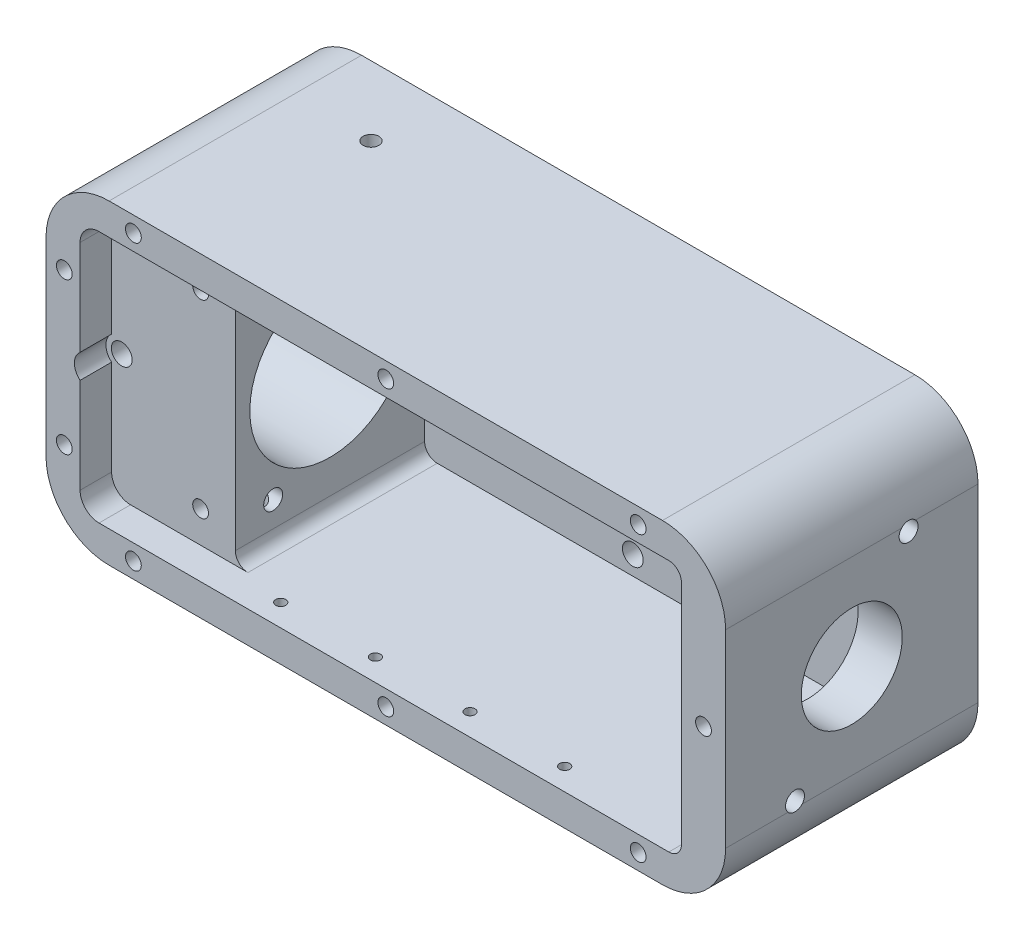
SolidWorks part; units mm, degrees
material "6061 Alloy"
ref_plane "Front" through (0, 0, 0) normal (0, 0, 1) x (1, 0, 0)
ref_plane "Top" through (0, 0, 0) normal (0, 1, 0) x (1, 0, 0)
ref_plane "Right" through (0, 0, 0) normal (1, 0, 0) x (0, 0, -1)
ref_plane "Plane1" through (0, 0, 40) normal (0, 0, 1) x (1, 0, 0)
sketch "Sketch1" plane through (0, 0, 40) normal (0, 0, 1) x (1, 0, 0)
  line L0 (0, -50) -> (107.7, -50)
  line L1 (107.7, -50) -> (107.7, 0)
  line L2 (107.7, 0) -> (0, 0)
  line L3 (0, 0) -> (0, -50)
extrude "Boss-Extrude1" add sketch "Sketch1" against normal blind 40
sketch "Sketch2" plane through (0, 0, 40) normal (0, 0, 1) x (1, 0, 0)
  line L0 (100.7, -45) -> (100.7, -5)
  line L1 (100.7, -5) -> (25, -5)
  line L2 (25, -5) -> (25, -45)
  line L3 (25, -45) -> (100.7, -45)
extrude "Cut-Extrude1" cut sketch "Sketch2" against normal blind 35
ref_plane "Plane2" through (0, 0, 35) normal (0, 0, -1) x (-1, 0, 0)
sketch "Sketch4" plane through (0, 0, 35) normal (0, 0, -1) x (-1, 0, 0)
  line L0 (-5.4, -5) -> (-25, -5)
  line L1 (-25, -5) -> (-25, -45)
  line L2 (-25, -45) -> (-5.4, -45)
  line L3 (-5.4, -45) -> (-5.4, -5)
extrude "Cut-Extrude2" cut sketch "Sketch4" against normal up to surface up to plane "Plane1"
sketch "Sketch5" plane through (0, 0, 0) normal (0, 0, -1) x (-1, 0, 0)
  line L0 (-99.7, -30.15) -> (-54.7, -30.15)
  line L1 (-54.7, -30.15) -> (-54.7, -19.85)
  line L2 (-54.7, -19.85) -> (-99.7, -19.85)
  line L3 (-99.7, -19.85) -> (-99.7, -30.15)
extrude "Cut-Extrude3" cut sketch "Sketch5" against normal through all
hole_wizard "M4x0.7 Tapped Hole1" positions "Sketch7" profile "Sketch6" tap size "M4x0.7" standard "ANSI Metric" end condition through all
sketch "Sketch7" plane through (0, 0, 0) normal (0, 0, -1) x (-1, 0, 0)
  point P0 (-58, -42)
  point P1 (-78, -42)
  point P2 (-98, -42)
  point P3 (-98, -8)
  point P4 (-58, -8)
  point P5 (-78, -8)
sketch "Sketch6" plane through (58, -42, 0) normal (1, 0, 0) x (0, 1, 0)
  line L0 (0, 0) -> (0, 40)
  line L1 (0, 40) -> (1.65, 40)
  line L2 (1.65, 40) -> (1.65, 0)
  line L5 (1.65, 0) -> (0, 0)
  line L11 (0, -6.35) -> (0, 107.95) construction
  dimension "Thru Tap Drill Dia." = 3.3
  dimension "Thru Tap Drill Depth" = 40
hole_wizard "Ø3.0mm Dowel Hole1" positions "Sketch9" profile "Sketch8" hole size "Ø3.0" standard "ANSI Metric" end condition through all
sketch "Sketch9" plane through (100.7, 0, 0) normal (-1, 0, 0) x (0, 0, 1)
  point P0 (11, -11)
sketch "Sketch8" plane through (100.7, -11, 11) normal (0, 1, 0) x (0, 0, 1)
  line L0 (0, 0) -> (0, 7)
  line L1 (0, 7) -> (1.5, 7)
  line L2 (1.5, 7) -> (1.5, 0)
  line L5 (1.5, 0) -> (0, 0)
  line L11 (0, -6.35) -> (0, 107.95) construction
  dimension "Thru Hole Dia." = 3
  dimension "Thru Hole Depth" = 7
hole_wizard "Ø3.0mm Dowel Hole2" positions "Sketch11" profile "Sketch10" hole size "Ø3.0" standard "ANSI Metric" end condition up to next
sketch "Sketch11" plane through (107.7, 0, 0) normal (1, 0, 0) x (0, 0, -1)
  point P0 (-29, -39)
sketch "Sketch10" plane through (107.7, -39, 29) normal (0, 1, 0) x (0, 0, -1)
  line L0 (0, 0) -> (0, 7)
  line L1 (0, 7) -> (1.5, 7)
  line L2 (1.5, 7) -> (1.5, 0)
  line L5 (1.5, 0) -> (0, 0)
  line L11 (0, -6.35) -> (0, 107.95) construction
  dimension "Thru Hole Dia." = 3
  dimension "Thru Hole Depth" = 7
hole_wizard "M3x0.5 Tapped Hole1" positions "Sketch13" profile "Sketch12" tap size "M3x0.5" standard "ANSI Metric"
sketch "Sketch13" plane through (0, 0, 0) normal (0, 1, 0) x (1, 0, 0)
  point P0 (22.5, -11)
sketch "Sketch12" plane through (22.5, 0, 11) normal (1, 0, 0) x (0, 0, 1)
  line L0 (0, 0) -> (0, 8.2511)
  line L1 (0, 8.2511) -> (1.25, 7.5)
  line L2 (1.25, 7.5) -> (1.25, 0)
  line L5 (1.25, 0) -> (0, 0)
  line L10 (0, 8.2511) -> (-1.25, 7.5) construction
  line L11 (0, -6.35) -> (0, 107.95) construction
  dimension "Tap Drill Dia." = 2.5
  dimension "Tap Drill Depth" = 7.5
  dimension "Drill Angle" = 118
hole_wizard "Ø3.0mm Dowel Hole3" positions "Sketch15" profile "Sketch14" hole size "Ø3.0" standard "ANSI Metric" end condition through all
sketch "Sketch15" plane through (25, 0, 0) normal (1, 0, 0) x (0, 0, -1)
  point P0 (-11, -11)
sketch "Sketch14" plane through (25, -11, 11) normal (0, 1, 0) x (0, 0, -1)
  line L0 (0, 0) -> (0, 25)
  line L1 (0, 25) -> (1.5, 25)
  line L2 (1.5, 25) -> (1.5, 0)
  line L5 (1.5, 0) -> (0, 0)
  line L11 (0, -6.35) -> (0, 107.95) construction
  dimension "Thru Hole Dia." = 3
  dimension "Thru Hole Depth" = 25
hole_wizard "Hole1" positions "Sketch17" profile "Sketch16" legacy
sketch "Sketch17" plane through (100.7, 0, 0) normal (-1, 0, 0) x (0, 0, 1)
  point P0 (20, -25)
sketch "Sketch16" plane through (100.7, -25, 20) normal (0, 1, 0) x (0, 0, 1)
  line L0 (0, 0) -> (0, 7)
  line L1 (0, 7) -> (8, 7)
  line L2 (8, 7) -> (8, 0)
  line L3 (8, 0) -> (0, 0)
  line L4 (0, 110) -> (0, -10) construction
  dimension "Diameter" = 16
  dimension "Depth" = 7
hole_wizard "M3x0.5 Tapped Hole2" positions "Sketch19" profile "Sketch18" tap size "M3x0.5" standard "ANSI Metric"
sketch "Sketch19" plane through (0, 0, 40) normal (0, 0, 1) x (1, 0, 0)
  point P0 (104.2, -25)
sketch "Sketch18" plane through (104.2, -25, 40) normal (1, 0, 0) x (0, -1, 0)
  line L0 (0, 0) -> (0, 8.2511)
  line L1 (0, 8.2511) -> (1.25, 7.5)
  line L2 (1.25, 7.5) -> (1.25, 0)
  line L5 (1.25, 0) -> (0, 0)
  line L10 (0, 8.2511) -> (-1.25, 7.5) construction
  line L11 (0, -6.35) -> (0, 107.95) construction
  dimension "Tap Drill Dia." = 2.5
  dimension "Tap Drill Depth" = 7.5
  dimension "Drill Angle" = 118
hole_wizard "Ø3.0mm Dowel Hole4" positions "Sketch21" profile "Sketch20" hole size "Ø3.0" standard "ANSI Metric" end condition through all
sketch "Sketch21" plane through (0, 0, 0) normal (-1, 0, 0) x (0, 0, 1)
  point P0 (29, -39)
sketch "Sketch20" plane through (0, -39, 29) normal (0, 1, 0) x (0, 0, 1)
  line L0 (0, 0) -> (0, 107.7)
  line L1 (0, 107.7) -> (1.5, 107.7)
  line L2 (1.5, 107.7) -> (1.5, 0)
  line L5 (1.5, 0) -> (0, 0)
  line L11 (0, -6.35) -> (0, 107.95) construction
  dimension "Thru Hole Dia." = 3
  dimension "Thru Hole Depth" = 107.7
hole_wizard "M3x0.5 Tapped Hole3" positions "Sketch23" profile "Sketch22" tap size "M3x0.5" standard "ANSI Metric"
sketch "Sketch23" plane through (0, 0, 40) normal (0, 0, 1) x (1, 0, 0)
  point P0 (2.9, -37)
  point P1 (93.85, -2.5)
  point P2 (53.85, -2.5)
  point P3 (13.85, -2.5)
  point P4 (2.9, -13)
  point P5 (13.85, -47.5)
  point P6 (53.85, -47.5)
  point P7 (93.85, -47.5)
sketch "Sketch22" plane through (2.9, -37, 40) normal (1, 0, 0) x (0, -1, 0)
  line L0 (0, 0) -> (0, 8.2511)
  line L1 (0, 8.2511) -> (1.25, 7.5)
  line L2 (1.25, 7.5) -> (1.25, 0)
  line L5 (1.25, 0) -> (0, 0)
  line L10 (0, 8.2511) -> (-1.25, 7.5) construction
  line L11 (0, -6.35) -> (0, 107.95) construction
  dimension "Tap Drill Dia." = 2.5
  dimension "Tap Drill Depth" = 7.5
  dimension "Drill Angle" = 118
hole_wizard "M3x0.5 Tapped Hole4" positions "Sketch25" profile "Sketch24" tap size "M3x0.5" standard "ANSI Metric" end condition up to next
sketch "Sketch25" plane through (0, -50, 0) normal (0, -1, 0) x (-1, 0, 0)
  point P0 (-22.5, -29)
sketch "Sketch24" plane through (22.5, -50, 29) normal (1, 0, 0) x (0, 0, -1)
  line L0 (0, 0) -> (0, 9.5)
  line L1 (0, 9.5) -> (1.25, 9.5)
  line L2 (1.25, 9.5) -> (1.25, 0)
  line L5 (1.25, 0) -> (0, 0)
  line L11 (0, -6.35) -> (0, 107.95) construction
  dimension "Thru Tap Drill Dia." = 2.5
  dimension "Thru Tap Drill Depth" = 9.5
hole_wizard "1 (1) Diameter Hole1" positions "Sketch27" profile "Sketch26" hole size "1" standard "ANSI Inch"
sketch "Sketch27" plane through (0, 0, 0) normal (-1, 0, 0) x (0, 0, 1)
  point P0 (20, -25)
sketch "Sketch26" plane through (0, -25, 20) normal (0, 1, 0) x (0, 0, 1)
  line L0 (0, 0) -> (0, 25)
  line L1 (0, 25) -> (12.7, 25)
  line L2 (12.7, 25) -> (12.7, 0)
  line L5 (12.7, 0) -> (0, 0)
  line L11 (0, -6.35) -> (0, 107.95) construction
  dimension "Thru Hole Dia." = 25.4
  dimension "Thru Hole Depth" = 25
ref_plane "Plane3" through (0, 0, 32.5924) normal (0, 0, -1) x (-1, 0, 0)
hole_wizard "M4x0.7 Tapped Hole2" positions "Sketch29" profile "Sketch28" tap size "M4x0.7" standard "ANSI Metric" end condition through all
sketch "Sketch29" plane through (0, 0, 32.5924) normal (0, 0, -1) x (-1, 0, 0)
  point P0 (-7, -25)
sketch "Sketch28" plane through (7, -25, 32.5924) normal (1, 0, 0) x (0, 1, 0)
  line L0 (0, 0) -> (0, 7.4076)
  line L1 (0, 7.4076) -> (1.65, 7.4076)
  line L2 (1.65, 7.4076) -> (1.65, 0)
  line L5 (1.65, 0) -> (0, 0)
  line L11 (0, -6.35) -> (0, 107.95) construction
  dimension "Thru Tap Drill Dia." = 3.3
  dimension "Thru Tap Drill Depth" = 7.4076
hole_wizard "M3x0.5 Tapped Hole5" positions "Sketch31" profile "Sketch30" tap size "M3x0.5" standard "ANSI Metric"
sketch "Sketch31" plane through (0, 0, 35) normal (0, 0, 1) x (1, 0, 0)
  point P0 (19.5, -10)
  point P1 (19.5, -40)
sketch "Sketch30" plane through (19.5, -10, 35) normal (1, 0, 0) x (0, -1, 0)
  line L0 (0, 0) -> (0, 5.7511)
  line L1 (0, 5.7511) -> (1.25, 5)
  line L2 (1.25, 5) -> (1.25, 0)
  line L5 (1.25, 0) -> (0, 0)
  line L10 (0, 5.7511) -> (-1.25, 5) construction
  line L11 (0, -6.35) -> (0, 107.95) construction
  dimension "Tap Drill Dia." = 2.5
  dimension "Tap Drill Depth" = 5
  dimension "Drill Angle" = 118
fillet "Fillet1" radius 2 8 edges at (99.7, -19.85, 2.5) (25, -5, 20) (100.7, -45, 22.5) (54.7, -30.15, 2.5) (100.7, -5, 22.5) (54.7, -19.85, 2.5) (25, -45, 20) (99.7, -30.15, 2.5) tangent propagation no
fillet "Fillet2" radius 3 2 edges at (5.4, -5, 37.5) (5.4, -45, 37.5) tangent propagation no
fillet "Fillet3" radius 10 4 edges at (0, 0, 20) (107.7, 0, 20) (0, -50, 20) (107.7, -50, 20) tangent propagation no
sketch "Sketch32" plane through (0, 0, 40) normal (0, 0, 1) x (1, 0, 0)
  circle A0 centre (7, -25) radius 2.5
  dimension "D1" = 5
extrude "Cut-Extrude4" cut sketch "Sketch32" against normal up to surface (5 mm away) up to face at (20.75, -10, 35)
hole_wizard "M2x0.4 Tapped Hole1" positions "Sketch33" profile "Sketch34" tap size "M2x0.4" standard "ANSI Metric"
sketch "Sketch33" plane through (0, -45, 0) normal (0, 1, 0) x (1, 0, 0)
  line L0 (33.7, -36.5) -> (78.7, -36.5) construction
  line L2 (97.7, -40) -> (10, -40) construction
  line L3 (107.7, -12.118) -> (107.7, -40) construction
  point P0 (33.7, -36.5)
  point P3 (48.7, -36.5)
  point P6 (63.7, -36.5)
  point P9 (78.7, -36.5)
  dimension "D1" = 3.5
  dimension "D2" = 29
  dimension "D3" = 15
  dimension "D4" = 15
  dimension "D5" = 15
sketch "Sketch34" plane through (33.7, -45, 36.5) normal (1, 0, 0) x (0, 0, 1)
  line L0 (0, 0) -> (0, 5.6807)
  line L1 (0, 5.6807) -> (0.8, 5.2)
  line L2 (0.8, 5.2) -> (0.8, 0)
  line L5 (0.8, 0) -> (0, 0)
  line L10 (0, 5.6807) -> (-0.8, 5.2) construction
  line L11 (0, -6.35) -> (0, 107.95) construction
  dimension "Tap Drill Dia." = 1.6
  dimension "Tap Drill Depth" = 5.2
  dimension "Drill Angle" = 118
